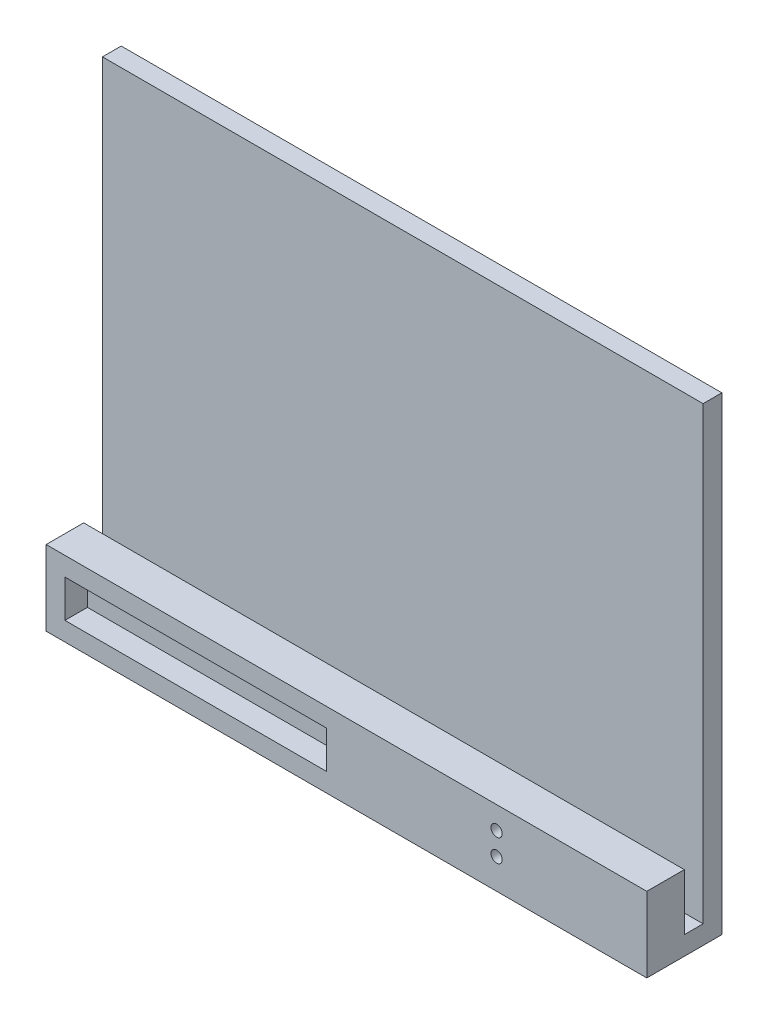
SolidWorks part; units mm, degrees
ref_plane "Front Plane" through (0, 0, 0) normal (0, 0, 1) x (1, 0, 0)
ref_plane "Top Plane" through (0, 0, 0) normal (0, 1, 0) x (1, 0, 0)
ref_plane "Right Plane" through (0, 0, 0) normal (1, 0, 0) x (0, 0, -1)
sketch "Sketch1" plane through (0, 0, 0) normal (0, 0, 1) x (1, 0, 0)
  line L1 (0, 158.75) -> (203.2, 158.75)
  line L2 (0, 158.75) -> (0, 0)
  line L3 (0, 0) -> (203.2, 0)
  line L4 (203.2, 158.75) -> (203.2, 0)
  point P4 (0, 0)
  dimension "D1" = 158.75
  dimension "D2" = 203.2
extrude "Boss-Extrude1" add sketch "Sketch1" along normal blind 6.35
sketch "Sketch2" plane through (0, 0, 6.35) normal (0, 0, 1) x (1, 0, 0)
  line L0 (0, 158.75) -> (0, 0) construction
  line L1 (0, 6.35) -> (203.2, 6.35)
  line L2 (0, 6.35) -> (0, 0)
  line L3 (0, 0) -> (203.2, 0)
  line L4 (203.2, 6.35) -> (203.2, 0)
  dimension "D1" = 6.35
extrude "Boss-Extrude2" add sketch "Sketch2" along normal blind 19.05
sketch "Sketch3" plane through (0, 6.35, 0) normal (0, 1, 0) x (1, 0, 0)
  line L6 (203.2, -25.4) -> (203.2, -6.35) construction
  line L7 (0, -25.4) -> (203.2, -25.4)
  line L8 (0, -25.4) -> (0, -12.7)
  line L9 (0, -12.7) -> (203.2, -12.7)
  line L10 (203.2, -25.4) -> (203.2, -12.7)
  dimension "D1" = 12.7
extrude "Boss-Extrude3" add sketch "Sketch3" along normal blind 19.05
sketch "Sketch4" plane through (0, 0, 25.4) normal (0, 0, 1) x (1, 0, 0)
  line L0 (0, 25.4) -> (0, 0) construction
  line L1 (6.35, 19.05) -> (94.9058, 19.05)
  line L2 (6.35, 19.05) -> (6.35, 6.35)
  line L3 (6.35, 6.35) -> (94.9058, 6.35)
  line L4 (94.9058, 19.05) -> (94.9058, 6.35)
  line L5 (0, 25.4) -> (203.2, 25.4) construction
  dimension "D1" = 6.35
  dimension "D2" = 12.7
  dimension "D3" = 6.35
extrude "Cut-Extrude1" cut sketch "Sketch4" against normal blind 7.62
sketch "Sketch5" plane through (0, 0, 25.4) normal (0, 0, 1) x (1, 0, 0)
  line L0 (152.4, 25.4) -> (152.4, 0) construction
  line L1 (0, 25.4) -> (203.2, 25.4) construction
  line L2 (0, 0) -> (203.2, 0) construction
  line L3 (203.2, 0) -> (203.2, 25.4) construction
  circle A0 centre (152.4, 17.78) radius 1.905
  circle A1 centre (152.4, 10.16) radius 1.905
  point P12 (0, 0)
  dimension "D1" = 3.81
  dimension "D2" = 3.81
  dimension "D3" = 50.8
  dimension "D4" = 10.16
  dimension "D5" = 7.62
extrude "Cut-Extrude2" cut sketch "Sketch5" against normal up to next
